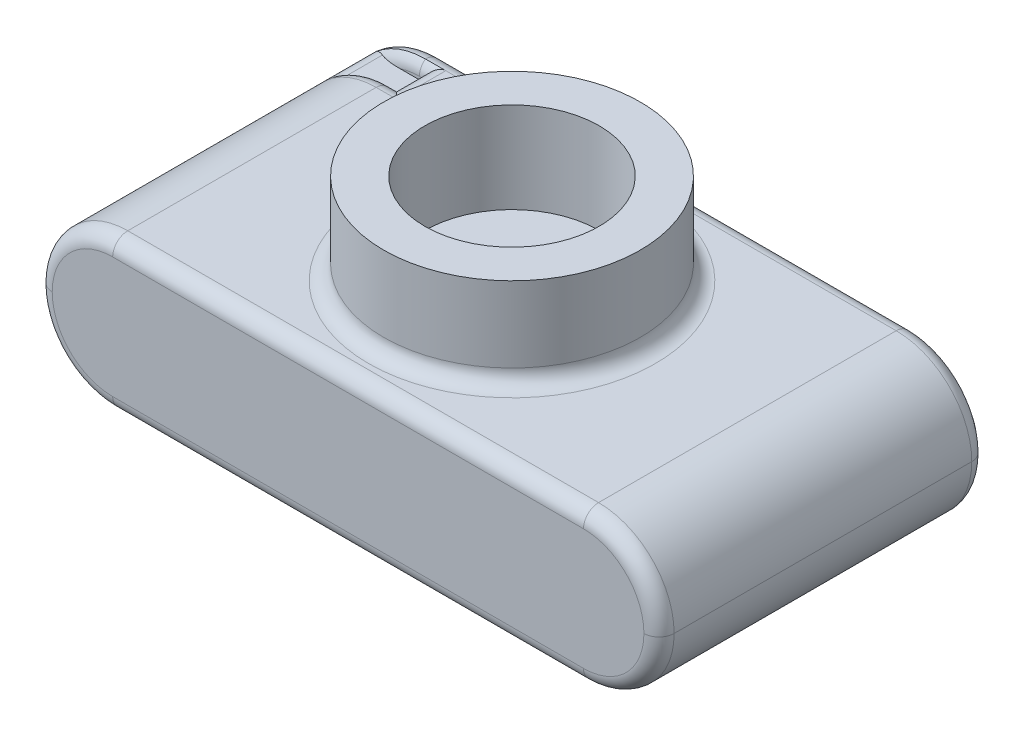
SolidWorks part; units mm, degrees
ref_plane "Front Plane" through (0, 0, 0) normal (0, 0, 1) x (1, 0, 0)
ref_plane "Top Plane" through (0, 0, 0) normal (0, 1, 0) x (1, 0, 0)
ref_plane "Right Plane" through (0, 0, 0) normal (1, 0, 0) x (0, 0, -1)
sketch "Sketch1" plane through (0, 0, 0) normal (0, 1, 0) x (1, 0, 0)
  line L1 (-20575.5167, 10846.9931) -> (20575.5167, 10846.9931)
  line L2 (-20575.5167, 10846.9931) -> (-20575.5167, -10846.9931)
  line L3 (-20575.5167, -10846.9931) -> (20575.5167, -10846.9931)
  line L4 (20575.5167, 10846.9931) -> (20575.5167, -10846.9931)
  line L5 (-20575.5167, 10846.9931) -> (20575.5167, -10846.9931) construction
  line L6 (-20575.5167, -10846.9931) -> (20575.5167, 10846.9931) construction
  point P0 (0, 0)
extrude "Boss-Extrude1" add sketch "Sketch1" along normal blind 10000
sketch "Sketch5" plane through (0, 0, -10846.9931) normal (0, 0, -1) x (-1, 0, 0)
  circle A0 centre (-16603.6638, 4539.4849) radius 2264.8198
extrude "Boss-Extrude3" add sketch "Sketch5" along normal blind 1000
sketch "Sketch6" plane through (0, 10000, 0) normal (0, 1, 0) x (1, 0, 0)
  line L1 (-20051.5828, 9449.7862) -> (-15225.1702, 9449.7862)
  line L2 (-20051.5828, 9449.7862) -> (-20051.5828, 7585.5339)
  line L3 (-20051.5828, 7585.5339) -> (-15225.1702, 7585.5339)
  line L4 (-15225.1702, 9449.7862) -> (-15225.1702, 7585.5339)
  line L5 (-20051.5828, 9449.7862) -> (-15225.1702, 7585.5339) construction
  line L6 (-20051.5828, 7585.5339) -> (-15225.1702, 9449.7862) construction
  point P0 (-17638.3765, 8517.66)
extrude "Cut-Extrude1" cut sketch "Sketch6" against normal blind 1000
sketch "Sketch10" plane through (0, 10000, 0) normal (0, 1, 0) x (1, 0, 0)
  circle A0 centre (0, 0) radius 8490.9463
  circle A1 centre (0, 0) radius 5767.811
extrude "Boss-Extrude4" add sketch "Sketch10" along normal blind 6000
fillet "Fillet1" radius 5000 4 edges at (20575.5167, 0, 0) (20575.5167, 10000, 0) (-20575.5167, 0, 0) (-20575.5167, 10000, 0)
fillet "Fillet2" radius 1000 6 edges at (19111.0506, 1464.4661, -10846.9931) (19111.0506, 8535.5339, -10846.9931) (-19111.0506, 8535.5339, -10846.9931) (-19111.0506, 1464.4661, -10846.9931) (0, 10000, -10846.9931) (0, 0, -10846.9931)
fillet "Fillet3" radius 1000 6 edges at (-19111.0506, 8535.5339, 10846.9931) (-19111.0506, 1464.4661, 10846.9931) (0, 0, 10846.9931) (19111.0506, 1464.4661, 10846.9931) (19111.0506, 8535.5339, 10846.9931) (0, 10000, 10846.9931)
fillet "Fillet4" radius 1000 6 edges at (-17156.6555, 9743.4165, -7585.5339) (-17156.6555, 9743.4165, -9449.7862) (0, 10000, 8490.9463) (-15400.3435, 10000, -7585.5339) (-15225.1702, 10000, -8517.66) (-15400.3435, 10000, -9449.7862)
fillet "Fillet5" radius 1000 1 edges at (-18575.5167, 9000, -8216.2635)
